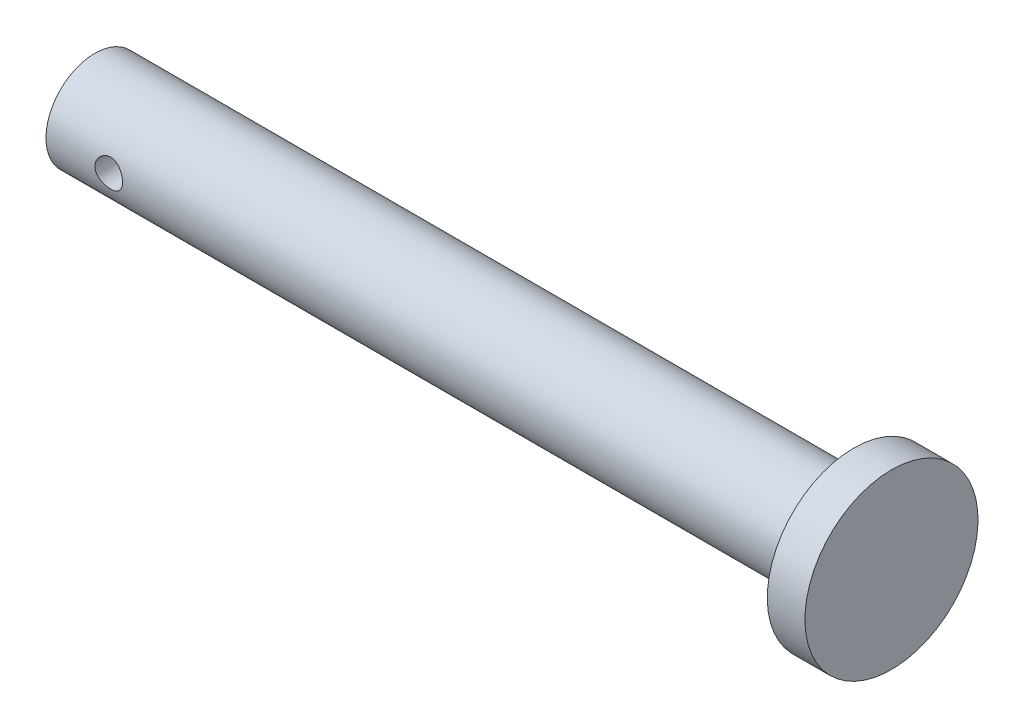
SolidWorks part; units mm, degrees
material "ABS"
ref_plane "Front Plane" through (0, 0, 0) normal (0, 0, 1) x (1, 0, 0)
ref_plane "Top Plane" through (0, 0, 0) normal (0, 1, 0) x (1, 0, 0)
ref_plane "Right Plane" through (0, 0, 0) normal (1, 0, 0) x (0, 0, -1)
sketch "Sketch2" plane through (0, 0, 0) normal (0, 0, 1) x (1, 0, 0)
  line L0 (0, 0) -> (0, -3.9) construction
  line L5 (-30.25, 0) -> (30.25, 0)
  line L6 (-30.25, 0) -> (-30.25, -3.9)
  line L7 (-30.25, -3.9) -> (30.25, -3.9)
  line L8 (30.25, 0) -> (30.25, -3.9)
  line L9 (-25.25, 0) -> (-25.25, 1.1) construction
  circle A0 centre (-25.25, 0) radius 1.1
  dimension "D1" = 55.5
  dimension "D2" = 3.9
  dimension "D3" = 1.1
  dimension "D4" = 5
revolve "Revolve2" add sketch "Sketch2" angle 360 about L5 region at (0.205, -1.962, 0)
extrude "Cut-Extrude1" cut sketch "Sketch2<3>" against normal through all both and the other way through all contours A0
sketch "Sketch2<3>" plane through (0, 0, 0) normal (0, 0, 1) x (1, 0, 0) same geometry as "Sketch2"
sketch "Sketch3" plane through (30.25, 0, 0) normal (1, 0, 0) x (0, 0, -1)
  line L0 (3.9, 0) -> (6.9, 0) construction
  circle A0 centre (0, 0) radius 6.9
  circle A1 centre (0, 0) radius 3.9 construction
  dimension "D1" = 3
extrude "Boss-Extrude1" add sketch "Sketch3" along normal blind 3
